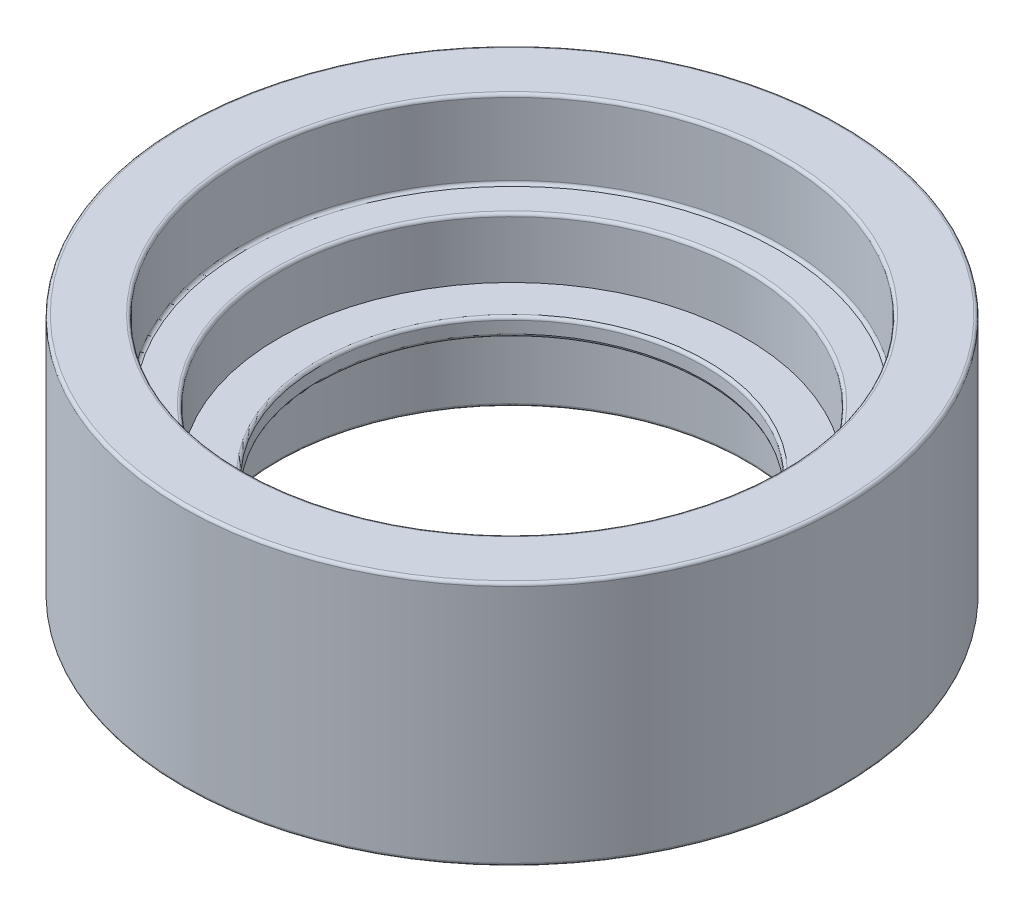
SolidWorks part; units mm, degrees
ref_plane "Front Plane" through (0, 0, 0) normal (0, 0, 1) x (1, 0, 0)
ref_plane "Top Plane" through (0, 0, 0) normal (0, 1, 0) x (1, 0, 0)
ref_plane "Right Plane" through (0, 0, 0) normal (1, 0, 0) x (0, 0, -1)
sketch "Sketch3" plane through (0, 0, 0) normal (0, 1, 0) x (1, 0, 0)
  circle A0 centre (0, 0) radius 39
  circle A1 centre (0, 0) radius 32
  circle A2 centre (0, 0) radius 45
  circle A3 centre (0, 0) radius 55
  dimension "D1" = 78
  dimension "D2" = 64
  dimension "D3" = 90
  dimension "D4" = 10
extrude "Boss-Extrude4" add sketch "Sketch3" along normal blind 1.5 and the other way blind 1.5 contours A0 A1 region at (-37.8969, 0, 0)
extrude "Boss-Extrude5" add sketch "Sketch3<3>" along normal blind 11.5 and the other way blind 16.5 contours A2 A0 region at (-43.7272, 0, 0)
sketch "Sketch3<3>" plane through (0, 0, 0) normal (0, 1, 0) x (1, 0, 0) same geometry as "Sketch3"
extrude "Boss-Extrude6" add sketch "Sketch3<4>" along normal blind 24.5 and the other way blind 16.5 contours A3 A2 region at (-53.4444, 0, 0)
sketch "Sketch3<4>" plane through (0, 0, 0) normal (0, 1, 0) x (1, 0, 0) same geometry as "Sketch3"
sketch "Sketch4" plane through (0, -16.5, 0) normal (0, -1, 0) x (1, 0, 0)
  line L0 (0, 39) -> (0, 55) construction
  circle A0 centre (0, 0) radius 39 construction
  circle A1 centre (0, 0) radius 39 construction
  circle A2 centre (0, 0) radius 55 construction
  circle A3 centre (0, 47) radius 2
  circle A4 centre (33.234, 33.234) radius 2
  circle A5 centre (47, 0) radius 2
  circle A6 centre (33.234, -33.234) radius 2
  circle A7 centre (0, -47) radius 2
  circle A8 centre (-33.234, -33.234) radius 2
  circle A9 centre (-47, 0) radius 2
  circle A10 centre (-33.234, 33.234) radius 2
  point P27 (0, 0)
  dimension "D1" = 8
extrude "Cut-Extrude1" cut sketch "Sketch4" against normal blind 10
fillet "Fillet1" radius 0.5 16 edges at (0, -16.5, 55) (0, -16.5, 39) (-33.234, -16.5, 31.234) (-47, -16.5, -2) (-33.234, -16.5, -35.234) (0, -16.5, -49) (33.234, -16.5, -35.234) (47, -16.5, -2) (33.234, -16.5, 31.234) (0, -16.5, 45) (0, 11.5, 45) (0, 11.5, 39) (0, 24.5, 55) (0, 24.5, 45) (0, -1.5, 32) (0, 1.5, 32)
